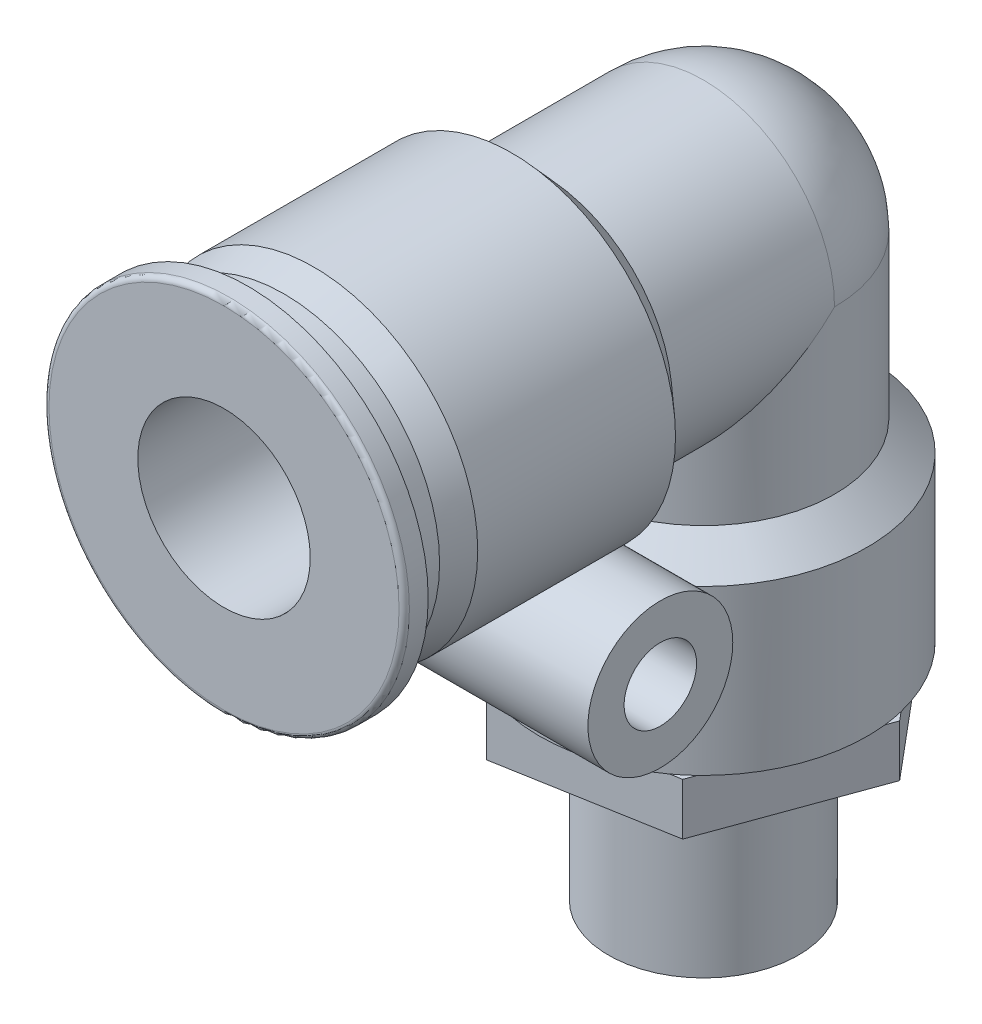
SolidWorks part; units mm, degrees
ref_plane "前视基准面" through (0, 0, 0) normal (0, 0, 1) x (1, 0, 0)
ref_plane "上视基准面" through (0, 0, 0) normal (0, 1, 0) x (1, 0, 0)
ref_plane "右视基准面" through (0, 0, 0) normal (1, 0, 0) x (0, 0, -1)
sketch "草图1" plane through (0, 0, 0) normal (1, 0, 0) x (0, 0, -1)
  line L0 (-27.8, 0) -> (-27.8, 10.15)
  line L1 (-27.5, 10.45) -> (-26.41, 10.45)
  line L2 (-26.41, 10.45) -> (-26.41, 7.5)
  line L3 (-26.41, 7.5) -> (-25.715, 7.5)
  line L4 (-25.715, 7.5) -> (-25.715, 8.825)
  line L5 (-25.515, 9.025) -> (-24.325, 9.025)
  line L6 (-24.325, 9.025) -> (-22.5875, 9.5)
  line L7 (-22.5875, 9.5) -> (-11.12, 9.5)
  line L8 (-11.12, 9.5) -> (-9.4092, 7.6)
  line L9 (-9.4092, 7.6) -> (0, 7.6)
  line L10 (7.6, 0) -> (-27.8, 0)
  line L11 (7.6, 0) -> (-27.8, 0) construction
  arc A0 (-27.8, 10.15) -> (-27.5, 10.45) centre (-27.5, 10.15) cw
  arc A1 (-25.715, 8.825) -> (-25.515, 9.025) centre (-25.515, 8.825) cw
  arc A2 (0, 7.6) -> (7.6, 0) centre (0, 0) cw
revolve "旋转1" add sketch "草图1" angle 360 about L11 reverse direction yes
sketch "草图2" plane through (0, 0, 0) normal (1, 0, 0) x (0, 0, -1)
  line L7 (-9.5, -20.6082) -> (-9.5, -11.12)
  line L8 (-9.5, -11.12) -> (-7.6, -9.4092)
  line L9 (-7.6, -9.4092) -> (-7.6, 0)
  line L10 (-7.6, 0) -> (0, 0)
  line L11 (0, 0) -> (0, -20.6082)
  line L12 (0, 0) -> (0, -20.6082) construction
  line L13 (-9.5, -20.6082) -> (0, -20.6082)
revolve "旋转2" add sketch "草图2" angle 360 about L12 reverse direction yes
sketch "草图3" plane through (0, 0, 0) normal (0, 0, 1) x (1, 0, 0)
  circle A0 centre (0, 0) radius 5
extrude "切除-拉伸1" cut sketch "草图3" along normal blind 27.8
sketch "草图4" plane through (0, 0, 0) normal (1, 0, 0) x (0, 0, -1)
  line L0 (5, 0) -> (5, -27.8)
  line L1 (5, -27.8) -> (0, -27.8)
  line L2 (0, -27.8) -> (0, 5)
  line L3 (0, -27.8) -> (0, 5) construction
  arc A0 (0, 5) -> (5, 0) centre (0, 0) cw
revolve "切除-旋转1" cut sketch "草图4" angle 360 about L3 reverse direction yes
sketch "草图5" plane through (0, 0, 0) normal (1, 0, 0) x (0, 0, -1)
  circle A0 centre (-12, -12) radius 4.2
extrude "凸台-拉伸1" add sketch "草图5" against normal blind 9.5 and the other way blind 9.5
sketch "草图6" plane through (0, 0, 0) normal (1, 0, 0) x (0, 0, -1)
  circle A0 centre (-12, -12) radius 2.1
extrude "切除-拉伸2" cut sketch "草图6" along normal blind 9.5 and the other way blind 9.5
sketch "草图7" plane through (0, -20.6082, 0) normal (0, -1, 0) x (1, 0, 0)
  line L1 (-6.3127, -7.5155) -> (3.3523, -9.2247)
  line L2 (3.3523, -9.2247) -> (9.665, -1.7092)
  line L3 (9.665, -1.7092) -> (6.3127, 7.5155)
  line L4 (6.3127, 7.5155) -> (-3.3523, 9.2247)
  line L5 (-3.3523, 9.2247) -> (-9.665, 1.7092)
  line L6 (-9.665, 1.7092) -> (-6.3127, -7.5155)
  circle A0 centre (0, 0) radius 8.5 construction
  circle A1 centre (0, 0) radius 5
  dimension "D1" = 17
extrude "凸台-拉伸2" add sketch "草图7" along normal blind 3
sketch "草图8" plane through (0, -23.6082, 0) normal (0, -1, 0) x (1, 0, 0)
  circle A0 centre (0, 0) radius 5
  circle A1 centre (0, 0) radius 5.5
  dimension "D1" = 11
extrude "凸台-拉伸3" add sketch "草图8" along normal blind 10
